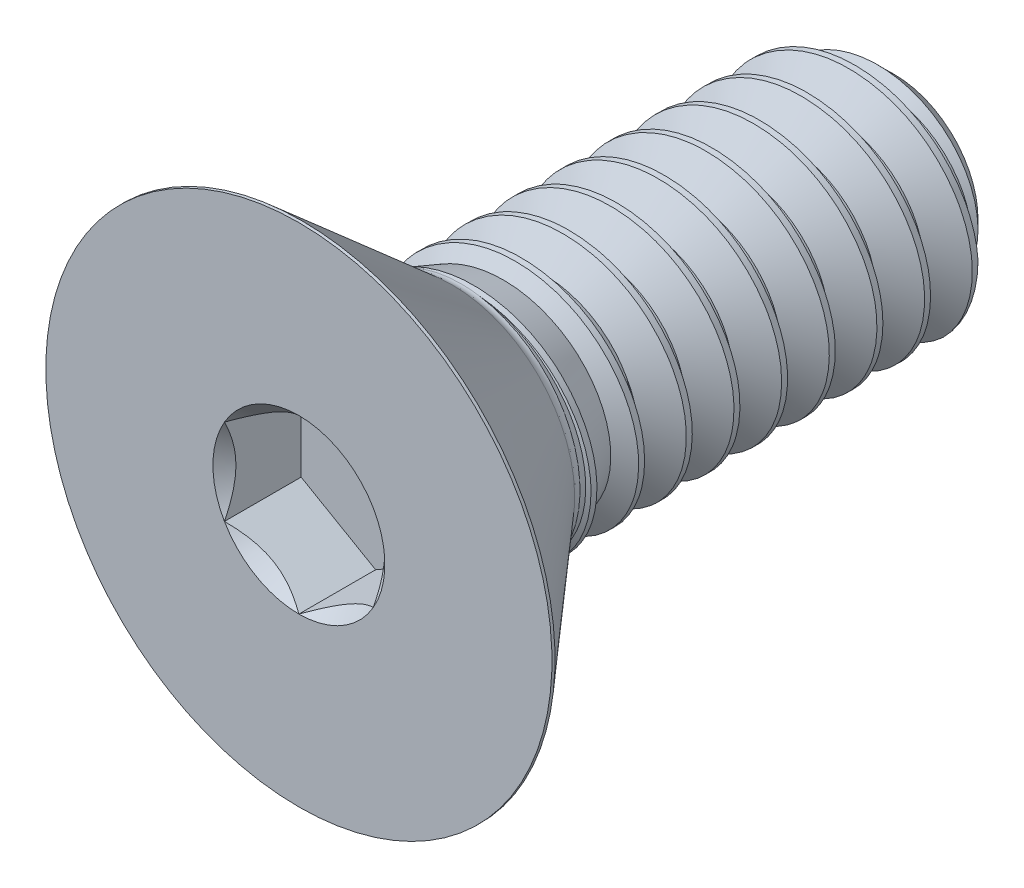
SolidWorks part; units mm, degrees
note: '?' marks a value the reader was unsure of.
material "Cast Alloy Steel"
ref_plane "Front Plane" through (0, 0, 0) normal (0, 0, 1) x (1, 0, 0)
ref_plane "Top Plane" through (0, 0, 0) normal (0, 1, 0) x (1, 0, 0)
ref_plane "Right Plane" through (0, 0, 0) normal (1, 0, 0) x (0, 0, -1)
sketch "Sketch1" plane through (0, 0, 0) normal (1, 0, 0) x (0, 0, -1)
  line L0 (-7.9375, 0) -> (7.9375, 0) construction
  line L1 (-7.9375, 0) -> (-7.9375, 6.7437)
  line L2 (-7.9375, 6.7437) -> (-7.8557, 6.7437)
  line L3 (-7.8557, 6.7437) -> (-3.8481, 3.2599)
  line L4 (-7.8557, -6.7437) -> (-3.8481, -3.2599)
  line L5 (7.9375, 0) -> (7.9375, 3.175)
  line L6 (7.9375, 3.175) -> (-3.8481, 3.175)
  line L7 (6.985, 3.175) -> (7.9375, 2.2225)
  line L8 (7.8581, 3.3125) -> (8.4931, 2.2126) construction
  line L9 (8.4931, 2.2126) -> (9.1281, 3.3125) construction
  line L10 (9.1281, 3.3125) -> (7.8581, 3.3125) construction
  line L11 (7.8978, 3.2437) -> (9.0884, 3.2437)
  line L12 (9.0884, 3.2437) -> (8.5725, 2.3501)
  line L13 (8.5725, 2.3501) -> (8.4138, 2.3501)
  line L14 (8.4138, 2.3501) -> (7.8978, 3.2437)
  line L15 (8.4931, 2.3501) -> (8.4931, 2.2126) construction
  line L16 (7.9375, 3.175) -> (9.0488, 3.175) construction
  line L17 (8.4931, 3.3125) -> (8.4931, 3.175) construction
  line L18 (7.9375, -3.175) -> (-3.8481, -3.175)
  arc A0 (-3.8481, 3.2599) -> (-3.6209, 3.175) centre (-3.6209, 3.5213) ccw
  point P2 (0, 0)
  point P23 (-5.8928, 0)
  point P27 (8.4931, 3.2437)
  point P30 (6.0325, -3.175)
  point P34 (-7.8557, -6.7437)
  dimension "Length" = 15.875
  dimension "Head Height" = 4.0894
  dimension "Head Diameter" = 13.4874
  dimension "Countersink Angle" = 82
  dimension "Thread Diameter" = 6.35
  dimension "D2" = 0.0818
  dimension "Pitch" = 1.27
  dimension "D4" = 0.1588
  dimension "D3" = 45
  dimension "D5" = 0.9525
  dimension "D6" = 2.0447
  dimension "D1" = 1.905
sketch "Sketch2" plane through (0, 0, 0) normal (0, 0, 1) x (1, 0, 0)
  line L1 (0, 2.2914) -> (-1.9844, 1.1457)
  line L2 (-1.9844, 1.1457) -> (-1.9844, -1.1457)
  line L3 (-1.9844, -1.1457) -> (0, -2.2914)
  line L4 (0, -2.2914) -> (1.9844, -1.1457)
  line L5 (1.9844, -1.1457) -> (1.9844, 1.1457)
  line L6 (1.9844, 1.1457) -> (0, 2.2914)
  circle A0 centre (0, 0) radius 1.9844 construction
  dimension "Drive Size" = 3.9688
sketch "Sketch11" plane through (0, 0, 0) normal (1, 0, 0) x (0, 0, -1)
  line L0 (-7.8557, 6.7437) -> (-3.8481, 3.2599) construction
  line L1 (-7.9375, 0) -> (-7.9375, 6.7437) construction
  line L2 (-7.8557, 6.7437) -> (-3.8481, 3.2599)
  line L3 (-7.9375, 0) -> (-7.9375, 6.7437)
  line L4 (-7.9375, 6.7437) -> (-7.8557, 6.7437) construction
  line L5 (-7.9375, 6.7437) -> (-7.8557, 6.7437)
  line L6 (-3.6209, 3.175) -> (6.985, 3.175)
  line L7 (6.985, 3.175) -> (7.9375, 2.2225)
  line L8 (7.9375, 2.2225) -> (7.9375, 0)
  line L9 (7.9375, 0) -> (-7.9375, 0)
  arc A0 (-3.8481, 3.2599) -> (-3.6209, 3.175) centre (-3.6209, 3.5213) ccw construction
  arc A1 (-3.8481, 3.2599) -> (-3.6209, 3.175) centre (-3.6209, 3.5213) ccw
revolve "Revolve1" add sketch "Sketch11" angle 360 about L9
sketch "Sketch9" plane through (0, 0, 7.9375) normal (0, 0, 1) x (1, 0, 0)
  line L0 (1.9844, -1.1457) -> (1.9844, 1.1457) construction
  line L1 (0, -2.2914) -> (1.9844, -1.1457) construction
  line L2 (-1.9844, -1.1457) -> (0, -2.2914) construction
  line L3 (-1.9844, 1.1457) -> (-1.9844, -1.1457) construction
  line L4 (0, 2.2914) -> (-1.9844, 1.1457) construction
  line L5 (1.9844, 1.1457) -> (0, 2.2914) construction
  line L6 (1.9844, -1.1457) -> (1.9844, 1.1457)
  line L7 (0, -2.2914) -> (1.9844, -1.1457)
  line L8 (-1.9844, -1.1457) -> (0, -2.2914)
  line L9 (-1.9844, 1.1457) -> (-1.9844, -1.1457)
  line L10 (0, 2.2914) -> (-1.9844, 1.1457)
  line L11 (1.9844, 1.1457) -> (0, 2.2914)
sketch "Sketch10" plane through (0, 0, 7.9375) normal (0, 0, 1) x (1, 0, 0)
  circle A0 centre (0, 0) radius 2.2914
extrude "Cut-Extrude2" cut sketch "Sketch10" against normal up to vertex (2.0447 mm away) draft 45 up to point (0, 0, 5.8928)
extrude "Cut-Extrude1" cut sketch "Sketch9" against normal up to vertex (2.0447 mm away) up to point (0, 0, 5.8928)
ref_plane "Plane1" through (0, 0, 3.6209) normal (0, 0, 1) x (1, 0, 0)
split "Split1" trim tools "Plane1" bodies to split 111 resulting bodies 105 106
sketch "Sketch3" plane through (0, 0, -7.9375) normal (0, 0, -1) x (-1, 0, 0)
  circle A0 centre (0, 0) radius 3.175 construction
  circle A1 centre (0, 0) radius 3.175
curve "Helix/Spiral1" pitch 1.27 height 15.875 turns 12.5
sketch "Sketch4" plane through (0, 0, 0) normal (1, 0, 0) x (0, 0, -1)
  line L0 (7.8978, 3.2437) -> (9.0884, 3.2437) construction
  line L1 (8.4138, 2.3501) -> (7.8978, 3.2437) construction
  line L2 (8.5725, 2.3501) -> (8.4138, 2.3501) construction
  line L3 (9.0884, 3.2437) -> (8.5725, 2.3501) construction
  line L4 (7.8978, 3.2437) -> (9.0884, 3.2437)
  line L5 (8.4138, 2.3501) -> (7.8978, 3.2437)
  line L6 (8.5725, 2.3501) -> (8.4138, 2.3501)
  line L7 (9.0884, 3.2437) -> (8.5725, 2.3501)
sweep "Cut-Sweep1" cut profiles "Sketch4" path "Helix/Spiral1" align with end faces yes
sketch "Sketch7" plane through (0, 0, 3.6209) normal (0, 0, 1) x (1, 0, 0)
  circle A0 centre (0, 0) radius 3.175
extrude "Boss-Extrude2" add sketch "Sketch7" against normal up to next (11.5584 mm away) draft 20
ref_axis "Axis1" through (0, 0, 3.6209) along (0, 0, -1)?
sketch "Sketch12" [suppressed] plane through (0, 0, 0) normal (1, 0, 0) x (0, 0, -1)
  line L0 (-5.8928, 2.2914) -> (-7.9375, 2.2914) construction
  line L1 (-5.8928, 2.2914) -> (-7.9375, 2.2914)
  line L2 (-5.8928, 2.2914) -> (-5.8928, 0)
  line L3 (-5.8928, 0) -> (-114.3, 0)
  line L4 (-114.3, 0) -> (-114.3, 23.8242)
  line L5 (-114.3, 23.8242) -> (-110.3312, 23.8242)
  line L6 (-110.3312, 23.8242) -> (-110.3312, 2.2914)
  line L7 (-110.3312, 2.2914) -> (-31.3944, 2.2914)
  line L8 (-31.3944, 2.2914) -> (-31.3944, 106.7298)
  line L9 (-31.3944, 106.7298) -> (-27.4256, 106.7298)
  line L10 (-27.4256, 106.7298) -> (-27.4256, 2.2914)
  line L11 (-27.4256, 2.2914) -> (-7.9375, 2.2914)
  dimension "D1" = 108.4072
  dimension "D2" = 3.9688
  dimension "D3" = 21.5328
  dimension "D4" = 25.5016
  dimension "D5" = 104.4384
revolve "Revolve2" [suppressed] add sketch "Sketch12" angle 360 about axis through (0, 0, 3.6209) along (0, 0, -1)
equation "\"D2@Sketch1\"=\"Head Height@Sketch1\"/50"
equation "\"D4@Sketch1\" = \"Pitch@Sketch1\" / 8"
equation "\"D5@Sketch1\"=\"Pitch@Sketch1\"*0.75"
equation "\"D4@Helix/Spiral1\"=\"Pitch@Sketch1\""
equation "\"D3@Helix/Spiral1\"=\"Length@Sketch1\""
equation "\"D6@Sketch1\"=\"Head Height@Sketch1\"/2"
equation "\"D1@Sketch1\"=\"Pitch@Sketch1\"*1.5"
